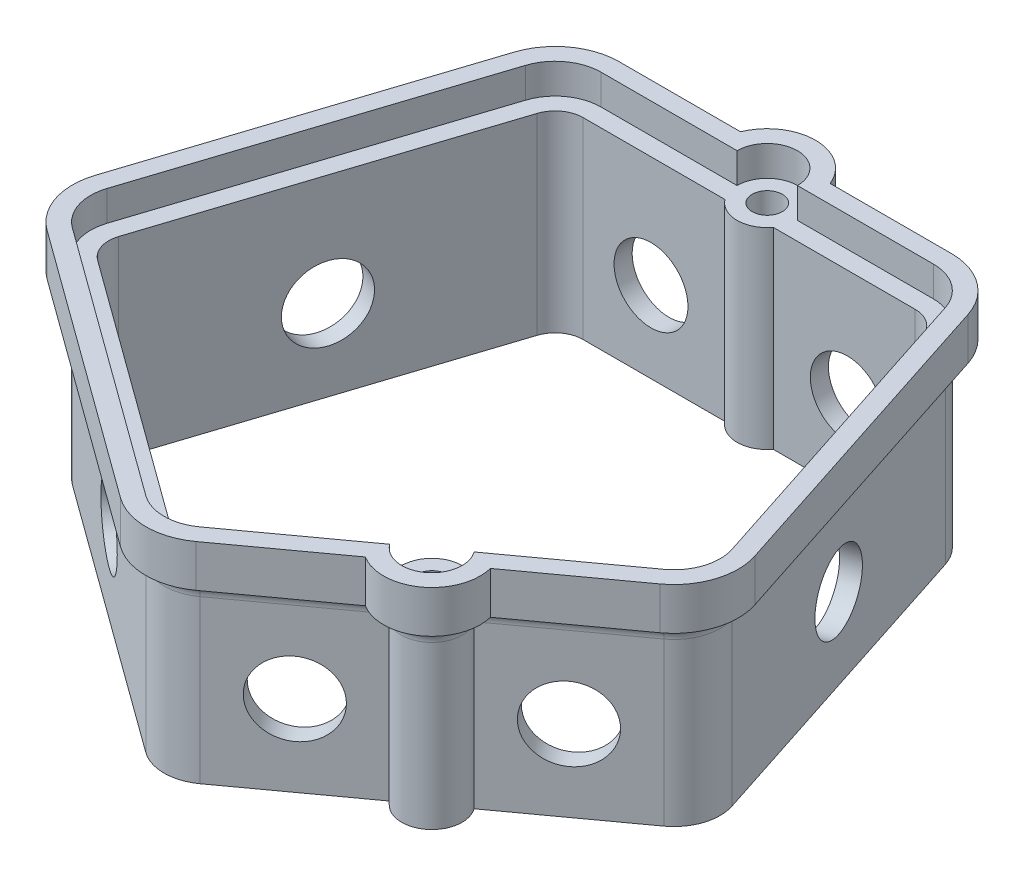
SolidWorks part; units mm, degrees
material "ABS"
ref_plane "Front Plane" through (0, 0, 0) normal (0, 0, 1) x (1, 0, 0)
ref_plane "Top Plane" through (0, 0, 0) normal (0, 1, 0) x (1, 0, 0)
ref_plane "Right Plane" through (0, 0, 0) normal (1, 0, 0) x (0, 0, -1)
sketch "Sketch1" plane through (0, 0, 0) normal (0, 1, 0) x (1, 0, 0)
  line L0 (-42.9604, -16.814) -> (1.5332, -49.1405)
  line L1 (6.9643, -49.1405) -> (25.975, -35.3284)
  line L2 (4.2488, 51.849) -> (4.2488, 50.849)
  line L3 (0.2488, 46.849) -> (-23.2498, 46.849)
  line L4 (-30.4968, 41.5837) -> (-47.4919, -10.7216)
  line L5 (-44.7237, -19.241) -> (-0.2302, -51.5675)
  line L6 (8.7277, -51.5675) -> (27.7384, -37.7554)
  line L7 (33.3256, -38.6403) -> (33.9134, -39.4494)
  line L8 (35.0196, -32.4654) -> (53.2213, -19.241)
  line L9 (55.9894, -10.7216) -> (38.9943, 41.5837)
  line L10 (31.7473, 46.849) -> (9.2488, 46.849)
  line L11 (32.4472, -30.6261) -> (51.4579, -16.814)
  line L12 (53.1362, -11.6487) -> (36.1412, 40.6567)
  line L13 (31.7473, 43.849) -> (8.2488, 43.849)
  line L14 (-23.2498, 43.849) -> (0.2488, 43.849)
  line L15 (-44.6387, -11.6487) -> (-27.6437, 40.6567)
  line L16 (-47.4919, -15.431) -> (47.4919, 15.431) construction
  line L17 (-44.6387, -14.504) -> (44.6387, 14.504) construction
  arc A0 (9.2488, 46.849) -> (4.2488, 51.849) centre (4.2488, 46.849) ccw
  arc A1 (4.2488, 50.849) -> (0.2488, 46.849) centre (4.2488, 46.849) ccw
  arc A2 (-23.2498, 46.849) -> (-30.4968, 41.5837) centre (-23.2498, 39.229) ccw
  arc A3 (-47.4919, -10.7216) -> (-44.7237, -19.241) centre (-40.2448, -13.0763) ccw
  arc A4 (-0.2302, -51.5675) -> (8.7277, -51.5675) centre (4.2488, -45.4028) ccw
  arc A5 (27.7384, -37.7554) -> (33.3256, -38.6403) centre (30.9745, -35.4043) ccw
  arc A6 (33.9134, -39.4494) -> (35.0196, -32.4654) centre (30.9745, -35.4043) ccw
  arc A7 (53.2213, -19.241) -> (55.9894, -10.7216) centre (48.7423, -13.0763) ccw
  arc A8 (38.9943, 41.5837) -> (31.7473, 46.849) centre (31.7473, 39.229) ccw
  arc A9 (-44.6387, -11.6487) -> (-42.9604, -16.814) centre (-40.2448, -13.0763) ccw
  arc A10 (1.5332, -49.1405) -> (6.9643, -49.1405) centre (4.2488, -45.4028) ccw
  circle A11 centre (30.9745, -35.4043) radius 2.5
  arc A12 (32.4472, -30.6261) -> (25.975, -35.3284) centre (30.9745, -35.4043) ccw
  arc A13 (51.4579, -16.814) -> (53.1362, -11.6487) centre (48.7423, -13.0763) ccw
  arc A14 (36.1412, 40.6567) -> (31.7473, 43.849) centre (31.7473, 39.229) ccw
  arc A15 (0.2488, 43.849) -> (8.2488, 43.849) centre (4.2488, 46.849) ccw
  circle A16 centre (4.2488, 46.849) radius 2.5
  arc A17 (-23.2498, 43.849) -> (-27.6437, 40.6567) centre (-23.2498, 39.229) ccw
  arc A36 (4.2488, 51.849) -> (-0.7512, 46.849) centre (4.2488, 46.849) ccw
  arc A37 (33.9134, -39.4494) -> (26.9294, -38.3432) centre (30.9745, -35.4043) cw
  point P58 (0, 0)
  point P60 (0, 0)
extrude "Boss-Extrude1" add sketch "Sketch1" along normal blind 40 contours L9 A8 L10 A0 L2 A1 L3 A2 L4 A3 L5 A4 L6 A5 L7 A6 L8 A7 A17 L14 A15 L13 A14 L12 A13 L11 A12 L1 A10 L0 A9 L15 A16 A11 | A37 L7 A5 L6 | L2 A36 L3 A1 region at (6.7388, 0, -49.339) region at (1.3722, 0, -49.7256) region at (30.3381, 0, 39.4223)
sketch "Sketch2" plane through (0, 40, 0) normal (0, 1, 0) x (1, 0, 0)
  line L1 (-30.4968, 41.5837) -> (-33.35, 42.5108)
  line L2 (-47.4919, -10.7216) -> (-50.345, -9.7946)
  line L3 (-33.35, 42.5108) -> (-50.345, -9.7946)
  line L5 (-23.2498, 46.849) -> (-23.2498, 49.849)
  line L8 (55.9894, -10.7216) -> (38.9943, 41.5837)
  line L9 (31.7473, 46.849) -> (9.2488, 46.849)
  line L10 (-0.7512, 46.849) -> (-23.2498, 46.849)
  line L13 (-30.4968, 41.5837) -> (-47.4919, -10.7216)
  line L21 (-44.7237, -19.241) -> (-0.2302, -51.5675)
  line L22 (8.7277, -51.5675) -> (26.9294, -38.3432)
  line L23 (35.0196, -32.4654) -> (53.2213, -19.241)
  line L24 (55.9894, -10.7216) -> (38.9943, 41.5837)
  line L25 (31.7473, 46.849) -> (9.2488, 46.849)
  line L26 (-0.7512, 46.849) -> (-23.2498, 46.849)
  line L27 (-30.4968, 41.5837) -> (-47.4919, -10.7216)
  line L28 (-44.7237, -19.241) -> (-0.2302, -51.5675)
  line L29 (8.7277, -51.5675) -> (26.9294, -38.3432)
  line L30 (35.0196, -32.4654) -> (53.2213, -19.241)
  line L31 (-23.2498, 49.849) -> (-3.1674, 49.849)
  line L33 (54.9846, -21.6681) -> (38.7377, -33.4722)
  line L34 (10.491, -53.9946) -> (26.738, -42.1905)
  line L35 (-1.9935, -53.9946) -> (-46.4871, -21.6681)
  line L36 (31.7473, 49.849) -> (11.665, 49.849)
  line L37 (41.8475, 42.5108) -> (58.8425, -9.7946)
  arc A0 (-3.1674, 49.849) -> (11.665, 49.849) centre (4.2488, 46.849) cw
  arc A1 (-33.35, 42.5108) -> (-23.2498, 49.849) centre (-23.2498, 39.229) cw
  arc A3 (-50.345, -9.7946) -> (-46.4871, -21.6681) centre (-40.2448, -13.0763) ccw
  arc A5 (41.8475, 42.5108) -> (31.7473, 49.849) centre (31.7473, 39.229) ccw
  arc A6 (58.8425, -9.7946) -> (54.9846, -21.6681) centre (48.7423, -13.0763) cw
  arc A21 (26.738, -42.1905) -> (38.7377, -33.4722) centre (30.9745, -35.4043) ccw
  arc A22 (-1.9935, -53.9946) -> (10.491, -53.9946) centre (4.2488, -45.4028) ccw
  arc A23 (38.9943, 41.5837) -> (31.7473, 46.849) centre (31.7473, 39.229) ccw
  arc A24 (9.2488, 46.849) -> (-0.7512, 46.849) centre (4.2488, 46.849) ccw
  arc A25 (-23.2498, 46.849) -> (-30.4968, 41.5837) centre (-23.2498, 39.229) ccw
  arc A26 (-47.4919, -10.7216) -> (-44.7237, -19.241) centre (-40.2448, -13.0763) ccw
  arc A27 (-0.2302, -51.5675) -> (8.7277, -51.5675) centre (4.2488, -45.4028) ccw
  arc A28 (26.9294, -38.3432) -> (35.0196, -32.4654) centre (30.9745, -35.4043) ccw
  arc A29 (53.2213, -19.241) -> (55.9894, -10.7216) centre (48.7423, -13.0763) ccw
  arc A30 (38.9943, 41.5837) -> (31.7473, 46.849) centre (31.7473, 39.229) ccw
  arc A31 (9.2488, 46.849) -> (-0.7512, 46.849) centre (4.2488, 46.849) ccw
  arc A32 (-23.2498, 46.849) -> (-30.4968, 41.5837) centre (-23.2498, 39.229) ccw
  arc A33 (-47.4919, -10.7216) -> (-44.7237, -19.241) centre (-40.2448, -13.0763) ccw
  arc A34 (-0.2302, -51.5675) -> (8.7277, -51.5675) centre (4.2488, -45.4028) ccw
  arc A35 (26.9294, -38.3432) -> (35.0196, -32.4654) centre (30.9745, -35.4043) ccw
  arc A36 (53.2213, -19.241) -> (55.9894, -10.7216) centre (48.7423, -13.0763) ccw
  line M62 (55.9894, -10.7216) -> (38.9943, 41.5837)
  arc M63 (38.9943, 41.5837) -> (31.7473, 46.849) centre (31.7473, 39.229) ccw
  line M64 (31.7473, 46.849) -> (9.2488, 46.849)
  arc M65 (9.2488, 46.849) -> (-0.7512, 46.849) centre (4.2488, 46.849) ccw
  line M66 (-0.7512, 46.849) -> (-23.2498, 46.849)
  arc M67 (-23.2498, 46.849) -> (-30.4968, 41.5837) centre (-23.2498, 39.229) ccw
  line M68 (-30.4968, 41.5837) -> (-47.4919, -10.7216)
  arc M69 (-47.4919, -10.7216) -> (-44.7237, -19.241) centre (-40.2448, -13.0763) ccw
  line M70 (-44.7237, -19.241) -> (-0.2302, -51.5675)
  arc M71 (-0.2302, -51.5675) -> (8.7277, -51.5675) centre (4.2488, -45.4028) ccw
  line M72 (8.7277, -51.5675) -> (26.9294, -38.3432)
  arc M73 (26.9294, -38.3432) -> (35.0196, -32.4654) centre (30.9745, -35.4043) ccw
  line M74 (35.0196, -32.4654) -> (53.2213, -19.241)
  arc M75 (53.2213, -19.241) -> (55.9894, -10.7216) centre (48.7423, -13.0763) ccw
  dimension "D5" = 3
  dimension "D2" = 3
  dimension "D3" = 3
  dimension "D1" = 0
extrude "Boss-Extrude2" add sketch "Sketch2" along normal blind 5 and the other way blind 2 contours L1 L3 L2 M68 | L35 A22 L34 A21 L33 A6 L37 A5 L36 A0 L31 L5 L2 A3 M66 M65 M64 M63 M62 M75 M74 M73 M72 M71 M70 M69 | A1 L1 L5 M67 region at (-40.4209, 40, -15.8946) region at (-28.3098, 40, -46.1935) region at (-48.9788, 40, 15.9142)
fillet "Fillet1" radius 3 14 edges at (20.498, 38, -46.849) (36.2262, 38, -45.3937) (47.4919, 38, -15.431) (55.9894, 38, 15.431) (-12.0005, 38, -46.849) (-27.7287, 38, -45.3937) (-38.9943, 38, -15.431) (-47.4919, 38, 15.431) (17.8285, 38, 44.9554) (4.2488, 38, 53.0228) (4.2488, 38, -51.849) (33.9134, 38, 39.4494) (44.1204, 38, 25.8532) (-22.477, 38, 35.4043)
sketch "Sketch3" plane through (0, 0, 0) normal (0, -1, 0) x (1, 0, 0)
  line L7 (-44.6387, 11.6487) -> (-27.6437, -40.6567)
  line L8 (1.5332, 49.1405) -> (-42.9604, 16.814)
  line L9 (25.975, 35.3284) -> (6.9643, 49.1405)
  line L10 (51.4579, 16.814) -> (32.4472, 30.6261)
  line L11 (36.1412, -40.6567) -> (53.1362, 11.6487)
  line L12 (8.2488, -43.849) -> (31.7473, -43.849)
  line L13 (-23.2498, -43.849) -> (0.2488, -43.849)
  line L14 (-44.6387, 11.6487) -> (-27.6437, -40.6567)
  line L15 (1.5332, 49.1405) -> (-42.9604, 16.814)
  line L16 (25.975, 35.3284) -> (6.9643, 49.1405)
  line L17 (51.4579, 16.814) -> (32.4472, 30.6261)
  line L18 (36.1412, -40.6567) -> (53.1362, 11.6487)
  line L19 (8.2488, -43.849) -> (31.7473, -43.849)
  line L20 (-23.2498, -43.849) -> (0.2488, -43.849)
  line L21 (38.9943, -41.5837) -> (55.9894, 10.7216)
  line L22 (53.2213, 19.241) -> (35.0196, 32.4654)
  line L23 (26.9294, 38.3432) -> (8.7277, 51.5675)
  line L24 (-0.2302, 51.5675) -> (-44.7237, 19.241)
  line L25 (-47.4919, 10.7216) -> (-30.4968, -41.5837)
  line L26 (-23.2498, -46.849) -> (-0.7512, -46.849)
  line L27 (9.2488, -46.849) -> (31.7473, -46.849)
  line L28 (38.9943, -41.5837) -> (55.9894, 10.7216)
  line L29 (53.2213, 19.241) -> (35.0196, 32.4654)
  line L30 (26.9294, 38.3432) -> (8.7277, 51.5675)
  line L31 (-0.2302, 51.5675) -> (-44.7237, 19.241)
  line L32 (-47.4919, 10.7216) -> (-30.4968, -41.5837)
  line L33 (-23.2498, -46.849) -> (-0.7512, -46.849)
  line L34 (9.2488, -46.849) -> (31.7473, -46.849)
  circle A1 centre (30.9745, 35.4043) radius 2.5
  circle A2 centre (30.9745, 35.4043) radius 2.5
  circle A3 centre (4.2488, -46.849) radius 2.5
  circle A4 centre (4.2488, -46.849) radius 2.5
  arc A7 (-27.6437, -40.6567) -> (-23.2498, -43.849) centre (-23.2498, -39.229) ccw
  arc A8 (-42.9604, 16.814) -> (-44.6387, 11.6487) centre (-40.2448, 13.0763) ccw
  arc A9 (6.9643, 49.1405) -> (1.5332, 49.1405) centre (4.2488, 45.4028) ccw
  arc A10 (25.975, 35.3284) -> (32.4472, 30.6261) centre (30.9745, 35.4043) ccw
  arc A11 (53.1362, 11.6487) -> (51.4579, 16.814) centre (48.7423, 13.0763) ccw
  arc A12 (31.7473, -43.849) -> (36.1412, -40.6567) centre (31.7473, -39.229) ccw
  arc A13 (8.2488, -43.849) -> (0.2488, -43.849) centre (4.2488, -46.849) ccw
  arc A14 (-27.6437, -40.6567) -> (-23.2498, -43.849) centre (-23.2498, -39.229) ccw
  arc A15 (-42.9604, 16.814) -> (-44.6387, 11.6487) centre (-40.2448, 13.0763) ccw
  arc A16 (6.9643, 49.1405) -> (1.5332, 49.1405) centre (4.2488, 45.4028) ccw
  arc A17 (25.975, 35.3284) -> (32.4472, 30.6261) centre (30.9745, 35.4043) ccw
  arc A18 (53.1362, 11.6487) -> (51.4579, 16.814) centre (48.7423, 13.0763) ccw
  arc A19 (31.7473, -43.849) -> (36.1412, -40.6567) centre (31.7473, -39.229) ccw
  arc A20 (8.2488, -43.849) -> (0.2488, -43.849) centre (4.2488, -46.849) ccw
  arc A25 (55.9894, 10.7216) -> (53.2213, 19.241) centre (48.7423, 13.0763) ccw
  arc A26 (35.0196, 32.4654) -> (26.9294, 38.3432) centre (30.9745, 35.4043) ccw
  arc A27 (8.7277, 51.5675) -> (-0.2302, 51.5675) centre (4.2488, 45.4028) ccw
  arc A28 (-44.7237, 19.241) -> (-47.4919, 10.7216) centre (-40.2448, 13.0763) ccw
  arc A29 (-30.4968, -41.5837) -> (-23.2498, -46.849) centre (-23.2498, -39.229) ccw
  arc A30 (-0.7512, -46.849) -> (9.2488, -46.849) centre (4.2488, -46.849) ccw
  arc A31 (31.7473, -46.849) -> (38.9943, -41.5837) centre (31.7473, -39.229) ccw
  arc A32 (55.9894, 10.7216) -> (53.2213, 19.241) centre (48.7423, 13.0763) ccw
  arc A33 (35.0196, 32.4654) -> (26.9294, 38.3432) centre (30.9745, 35.4043) ccw
  arc A34 (8.7277, 51.5675) -> (-0.2302, 51.5675) centre (4.2488, 45.4028) ccw
  arc A35 (-44.7237, 19.241) -> (-47.4919, 10.7216) centre (-40.2448, 13.0763) ccw
  arc A36 (-30.4968, -41.5837) -> (-23.2498, -46.849) centre (-23.2498, -39.229) ccw
  arc A37 (-0.7512, -46.849) -> (9.2488, -46.849) centre (4.2488, -46.849) ccw
  arc A38 (31.7473, -46.849) -> (38.9943, -41.5837) centre (31.7473, -39.229) ccw
  dimension "D1" = 0
  dimension "D2" = 0
  dimension "D3" = 0
  dimension "D4" = 0
extrude "Boss-Extrude3" add sketch "Sketch3" along normal blind 7
sketch "Sketch4" plane through (0, -7, 0) normal (0, -1, 0) x (1, 0, 0)
  line L7 (-23.2498, -43.849) -> (0.2488, -43.849)
  line L8 (-44.6387, 11.6487) -> (-27.6437, -40.6567)
  line L9 (1.5332, 49.1405) -> (-42.9604, 16.814)
  line L10 (25.975, 35.3284) -> (6.9643, 49.1405)
  line L11 (51.4579, 16.814) -> (32.4472, 30.6261)
  line L12 (36.1412, -40.6567) -> (53.1362, 11.6487)
  line L13 (8.2488, -43.849) -> (31.7473, -43.849)
  line L14 (-23.2498, -43.849) -> (0.2488, -43.849)
  line L15 (-44.6387, 11.6487) -> (-27.6437, -40.6567)
  line L16 (1.5332, 49.1405) -> (-42.9604, 16.814)
  line L17 (25.975, 35.3284) -> (6.9643, 49.1405)
  line L18 (51.4579, 16.814) -> (32.4472, 30.6261)
  line L19 (36.1412, -40.6567) -> (53.1362, 11.6487)
  line L20 (8.2488, -43.849) -> (31.7473, -43.849)
  line L21 (38.9943, -41.5837) -> (55.9894, 10.7216)
  line L22 (53.2213, 19.241) -> (35.0196, 32.4654)
  line L23 (26.9294, 38.3432) -> (8.7277, 51.5675)
  line L24 (-0.2302, 51.5675) -> (-44.7237, 19.241)
  line L25 (-47.4919, 10.7216) -> (-30.4968, -41.5837)
  line L26 (-23.2498, -46.849) -> (-0.7512, -46.849)
  line L27 (9.2488, -46.849) -> (31.7473, -46.849)
  line L28 (38.9943, -41.5837) -> (55.9894, 10.7216)
  line L29 (53.2213, 19.241) -> (35.0196, 32.4654)
  line L30 (26.9294, 38.3432) -> (8.7277, 51.5675)
  line L31 (-0.2302, 51.5675) -> (-44.7237, 19.241)
  line L32 (-47.4919, 10.7216) -> (-30.4968, -41.5837)
  line L33 (-23.2498, -46.849) -> (-0.7512, -46.849)
  line L34 (9.2488, -46.849) -> (31.7473, -46.849)
  circle A1 centre (30.9745, 35.4043) radius 2.5
  circle A2 centre (30.9745, 35.4043) radius 2.5
  circle A3 centre (4.2488, -46.849) radius 2.5
  circle A4 centre (4.2488, -46.849) radius 2.5
  arc A7 (-27.6437, -40.6567) -> (-23.2498, -43.849) centre (-23.2498, -39.229) ccw
  arc A8 (-42.9604, 16.814) -> (-44.6387, 11.6487) centre (-40.2448, 13.0763) ccw
  arc A9 (6.9643, 49.1405) -> (1.5332, 49.1405) centre (4.2488, 45.4028) ccw
  arc A10 (25.975, 35.3284) -> (32.4472, 30.6261) centre (30.9745, 35.4043) ccw
  arc A11 (53.1362, 11.6487) -> (51.4579, 16.814) centre (48.7423, 13.0763) ccw
  arc A12 (31.7473, -43.849) -> (36.1412, -40.6567) centre (31.7473, -39.229) ccw
  arc A13 (8.2488, -43.849) -> (0.2488, -43.849) centre (4.2488, -46.849) ccw
  arc A14 (-27.6437, -40.6567) -> (-23.2498, -43.849) centre (-23.2498, -39.229) ccw
  arc A15 (-42.9604, 16.814) -> (-44.6387, 11.6487) centre (-40.2448, 13.0763) ccw
  arc A16 (6.9643, 49.1405) -> (1.5332, 49.1405) centre (4.2488, 45.4028) ccw
  arc A17 (25.975, 35.3284) -> (32.4472, 30.6261) centre (30.9745, 35.4043) ccw
  arc A18 (53.1362, 11.6487) -> (51.4579, 16.814) centre (48.7423, 13.0763) ccw
  arc A19 (31.7473, -43.849) -> (36.1412, -40.6567) centre (31.7473, -39.229) ccw
  arc A20 (8.2488, -43.849) -> (0.2488, -43.849) centre (4.2488, -46.849) ccw
  arc A25 (31.7473, -46.849) -> (38.9943, -41.5837) centre (31.7473, -39.229) ccw
  arc A26 (55.9894, 10.7216) -> (53.2213, 19.241) centre (48.7423, 13.0763) ccw
  arc A27 (35.0196, 32.4654) -> (26.9294, 38.3432) centre (30.9745, 35.4043) ccw
  arc A28 (8.7277, 51.5675) -> (-0.2302, 51.5675) centre (4.2488, 45.4028) ccw
  arc A29 (-44.7237, 19.241) -> (-47.4919, 10.7216) centre (-40.2448, 13.0763) ccw
  arc A30 (-30.4968, -41.5837) -> (-23.2498, -46.849) centre (-23.2498, -39.229) ccw
  arc A31 (-0.7512, -46.849) -> (9.2488, -46.849) centre (4.2488, -46.849) ccw
  arc A32 (31.7473, -46.849) -> (38.9943, -41.5837) centre (31.7473, -39.229) ccw
  arc A33 (55.9894, 10.7216) -> (53.2213, 19.241) centre (48.7423, 13.0763) ccw
  arc A34 (35.0196, 32.4654) -> (26.9294, 38.3432) centre (30.9745, 35.4043) ccw
  arc A35 (8.7277, 51.5675) -> (-0.2302, 51.5675) centre (4.2488, 45.4028) ccw
  arc A36 (-44.7237, 19.241) -> (-47.4919, 10.7216) centre (-40.2448, 13.0763) ccw
  arc A37 (-30.4968, -41.5837) -> (-23.2498, -46.849) centre (-23.2498, -39.229) ccw
  arc A38 (-0.7512, -46.849) -> (9.2488, -46.849) centre (4.2488, -46.849) ccw
  dimension "D1" = 0
  dimension "D2" = 0
  dimension "D3" = 0
  dimension "D4" = 0
extrude "Cut-Extrude1" cut sketch "Sketch4" against normal blind 15.17
sketch "Sketch5" plane through (-24.6013, 0, 33.8608) normal (-0.5878, 0, 0.809) x (0.809, 0, 0.5878)
  line L0 (-24.8727, 35) -> (30.1244, 8.17) construction
  line L1 (30.1244, 8.17) -> (30.1244, 35) construction
  line L2 (30.1244, 35) -> (-24.8727, 8.17) construction
  line L3 (-24.8727, 8.17) -> (-24.8727, 35) construction
  circle A0 centre (2.6259, 21.585) radius 6.12
  dimension "D1" = 12.24
extrude "Cut-Extrude2" cut sketch "Sketch5" against normal up to surface (3 mm away) up to face at (-20.7136, 24.085, 32.9772)
sketch "Sketch6" plane through (0, 0, -46.849) normal (0, 0, -1) x (-1, 0, 0)
  line L0 (-31.7473, 8.17) -> (-9.2488, 35) construction
  line L1 (-9.2488, 35) -> (-31.7473, 35) construction
  line L2 (-31.7473, 35) -> (-9.2488, 8.17) construction
  line L3 (0.7512, 8.17) -> (23.2498, 35) construction
  line L4 (23.2498, 35) -> (23.2498, 8.17) construction
  line L5 (23.2498, 8.17) -> (0.7512, 35) construction
  circle A0 centre (-20.498, 21.585) radius 6.12
  circle A1 centre (12.0005, 21.585) radius 6.12
  dimension "D1" = 12.24
extrude "Cut-Extrude3" cut sketch "Sketch6" against normal up to surface (3 mm away) up to face at (19.998, 24.085, -43.849)
sketch "Sketch8" plane through (27.5371, 0, 37.9016) normal (0.5878, 0, 0.809) x (0.809, 0, -0.5878)
  line L0 (-0.7512, 35) -> (-23.2498, 8.17) construction
  line L1 (-23.2498, 8.17) -> (-23.2498, 35) construction
  line L2 (-23.2498, 35) -> (-0.7512, 8.17) construction
  line L3 (9.2488, 35) -> (31.7473, 8.17) construction
  line L4 (31.7473, 8.17) -> (9.2488, 8.17) construction
  line L5 (9.2488, 8.17) -> (31.7473, 35) construction
  line L6 (31.7473, 35) -> (9.2488, 35) construction
  circle A0 centre (-12.0005, 21.585) radius 6.12
  circle A1 centre (20.498, 21.585) radius 6.12
  dimension "D1" = 12.24
extrude "Cut-Extrude4" cut sketch "Sketch8" against normal up to surface (3 mm away) up to face at (41.9525, 24.085, 23.72)
sketch "Sketch10" plane through (-39.8058, 0, -12.9337) normal (-0.9511, 0, -0.309) x (-0.309, 0, 0.9511)
  line L0 (-30.1244, 8.17) -> (24.8727, 35) construction
  line L1 (24.8727, 35) -> (24.8727, 8.17) construction
  line L2 (24.8727, 35) -> (24.8727, 8.17) construction
  line L3 (24.8727, 8.17) -> (-30.1244, 8.17) construction
  line L4 (24.8727, 8.17) -> (-30.1244, 35) construction
  circle A0 centre (-2.6259, 21.585) radius 6.12
  dimension "D1" = 12.24
extrude "Cut-Extrude5" cut sketch "Sketch10" against normal up to surface (3 mm away) up to face at (-36.1412, 24.085, -14.504)
sketch "Sketch11" plane through (47.4919, 0, -15.431) normal (0.9511, 0, -0.309) x (-0.309, 0, -0.9511)
  line L0 (27.4985, 8.17) -> (-27.4985, 35) construction
  line L1 (-27.4985, 35) -> (-27.4985, 8.17) construction
  line L2 (-27.4985, 8.17) -> (27.4985, 35) construction
  circle A0 centre (0, 21.585) radius 6.12
  dimension "D1" = 12.24
extrude "Cut-Extrude6" cut sketch "Sketch11" against normal up to surface (3 mm away) up to face at (44.6387, 24.085, -14.504)
